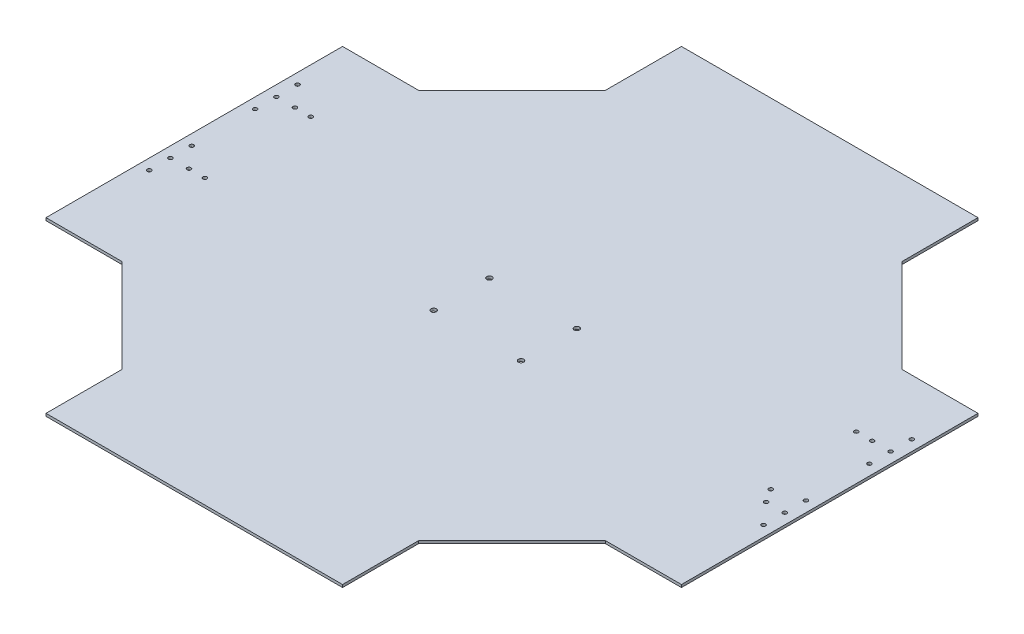
SolidWorks part; units mm, degrees
material "Acrylic (Medium-high impact)"
ref_plane "Front Plane" through (0, 0, 0) normal (0, 0, 1) x (1, 0, 0)
ref_plane "Top Plane" through (0, 0, 0) normal (0, 1, 0) x (1, 0, 0)
ref_plane "Right Plane" through (0, 0, 0) normal (1, 0, 0) x (0, 0, -1)
sketch "Sketch1" plane through (0, 0, 0) normal (0, 1, 0) x (1, 0, 0)
  line L0 (-381, 177.8) -> (-289.7187, 177.8)
  line L1 (-177.8, -381) -> (177.8, -381)
  line L2 (-381, -177.8) -> (-381, 177.8)
  line L3 (-177.8, 381) -> (177.8, 381)
  line L4 (381, -177.8) -> (381, 177.8)
  line L5 (0, 381) -> (0, -381) construction
  line L6 (-381, 0) -> (381, 0) construction
  line L7 (-289.7187, 177.8) -> (-177.8, 289.7188)
  line L8 (-177.8, 289.7188) -> (-177.8, 381)
  line L9 (177.8, 289.7188) -> (177.8, 381)
  line L10 (289.7187, 177.8) -> (177.8, 289.7188)
  line L11 (381, 177.8) -> (289.7187, 177.8)
  line L12 (-381, -177.8) -> (-289.7187, -177.8)
  line L13 (-177.8, -289.7188) -> (-177.8, -381)
  line L14 (381, -177.8) -> (289.7187, -177.8)
  line L15 (177.8, -289.7188) -> (177.8, -381)
  line L16 (289.7187, -177.8) -> (177.8, -289.7188)
  line L17 (-289.7187, -177.8) -> (-177.8, -289.7188)
  point P0 (0, 0)
  dimension "D1" = 762
  dimension "D2" = 135
  dimension "D3" = 203.2
  dimension "D4" = 91.2812
extrude "Boss-Extrude1" add sketch "Sketch1" along normal mid plane 3.175
sketch "Sketch2" plane through (0, 1.5875, 0) normal (0, 1, 0) x (1, 0, 0)
  line L0 (-346.075, -41.275) -> (49653.925, -41.275) construction
  line L1 (-368.3, -66.675) -> (-368.3, -15.875) construction
  line L2 (-381, 177.8) -> (-381, -177.8) construction
  line L3 (0, 0) -> (0, 50000) construction
  line L4 (368.3, -66.675) -> (368.3, -15.875) construction
  line L5 (-177.8, -381) -> (177.8, -381) construction
  line L6 (-368.3, 60.325) -> (-368.3, 111.125) construction
  line L7 (-488.2597, 85.725) -> (49511.7403, 85.725) construction
  line L8 (368.3, 60.325) -> (368.3, 111.125) construction
  circle A0 centre (-346.075, -41.275) radius 2.3813
  circle A1 centre (-368.3, -41.275) radius 2.3813
  circle A2 centre (-368.3, -15.875) radius 2.3813
  circle A3 centre (-368.3, -66.675) radius 2.3813
  circle A4 centre (368.3, -66.675) radius 2.3813
  circle A5 centre (368.3, -15.875) radius 2.3813
  circle A6 centre (368.3, -41.275) radius 2.3813
  circle A7 centre (346.075, -41.275) radius 2.3813
  circle A8 centre (-327.025, -41.275) radius 2.3813
  circle A9 centre (335.6948, -25.3015) radius 2.3813
  circle A10 centre (-346.075, 85.725) radius 2.3813
  circle A11 centre (-368.3, 85.725) radius 2.3813
  circle A12 centre (-368.3, 111.125) radius 2.3813
  circle A13 centre (-368.3, 60.325) radius 2.3813
  circle A14 centre (-327.025, 85.725) radius 2.3813
  circle A15 centre (327.025, 85.725) radius 2.3813
  circle A16 centre (368.3, 60.325) radius 2.3813
  circle A17 centre (368.3, 111.125) radius 2.3813
  circle A18 centre (368.3, 85.725) radius 2.3813
  circle A19 centre (346.075, 85.725) radius 2.3813
  point P0 (-444.9251, 75.9005)
  point P15 (-368.3, -41.275)
  point P25 (368.3, -41.275)
  point P42 (-368.3, 85.725)
  point P56 (368.3, 85.725)
  dimension "D1" = 4.7625
  dimension "D5" = 19.05
  dimension "D6" = 19.05
  dimension "D8" = 4.7625
  dimension "D2" = 50.8
  dimension "D3" = 22.225
  dimension "D4" = 12.7
  dimension "D7" = 339.725
  dimension "D9" = 50.8
  dimension "D10" = 19.05
  dimension "D11" = 127
extrude "Cut-Extrude1" cut sketch "Sketch2" against normal through all
sketch "Sketch4" plane through (0, 1.5875, 0) normal (0, 1, 0) x (1, 0, 0)
  line L0 (0, 0) -> (0, 118.0607) construction
  line L1 (-177.8, -381) -> (177.8, -381) construction
  circle A0 centre (-52.3875, -41.5727) radius 3.175
  circle A1 centre (52.3875, -41.5727) radius 3.175
  circle A2 centre (-52.3875, 25.3008) radius 3.175
  circle A3 centre (52.3875, 25.3008) radius 3.175
  point P13 (0, 0)
  point P14 (56.3415, 28.0066)
  point P15 (0, 0)
  point P16 (0, 0)
  dimension "D1" = 6.35
  dimension "D4" = 66.8734
  dimension "D2" = 104.775
  dimension "D3" = 339.4273
extrude "Cut-Extrude3" cut sketch "Sketch4" against normal through all and the other way through all
